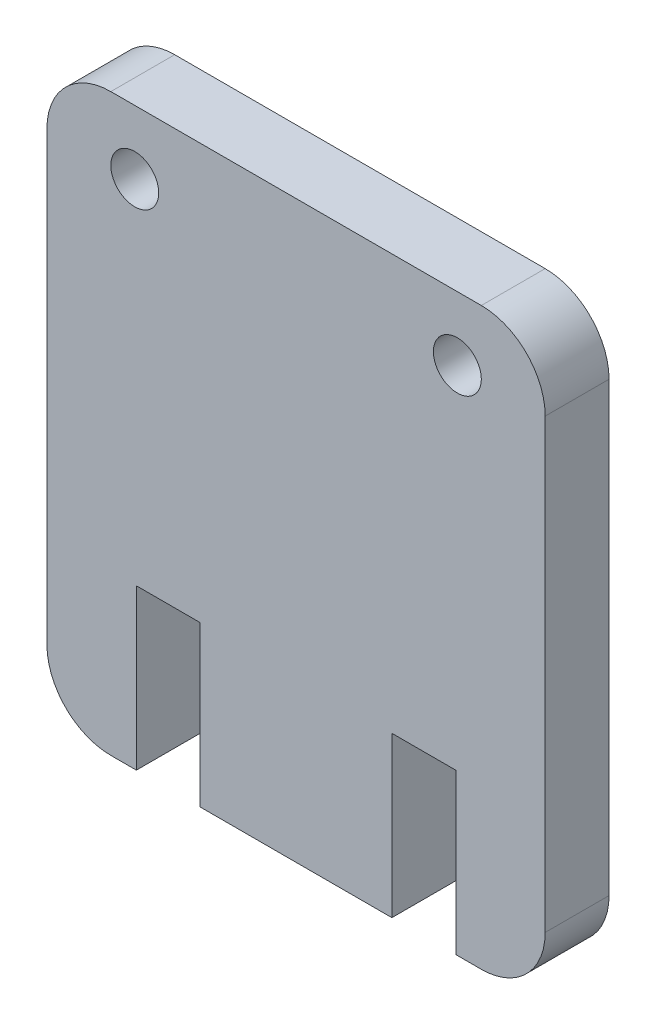
SolidWorks part; units mm, degrees
material "Acrylic (Medium-high impact)"
ref_plane "Front Plane" through (0, 0, 0) normal (0, 0, 1) x (1, 0, 0)
ref_plane "Top Plane" through (0, 0, 0) normal (0, 1, 0) x (1, 0, 0)
ref_plane "Right Plane" through (0, 0, 0) normal (1, 0, 0) x (0, 0, -1)
sketch "Model" plane through (0, 0, 0) normal (0, 0, 1) x (1, 0, 0)
  line L0 (2, 0) -> (2.8, 0)
  line L1 (2.8, 0) -> (2.8, 5)
  line L2 (2.8, 5) -> (4.8, 5)
  line L3 (4.8, 5) -> (4.8, 0)
  line L4 (4.8, 0) -> (10.8, 0)
  line L5 (10.8, 0) -> (10.8, 5)
  line L6 (10.8, 5) -> (12.8, 5)
  line L7 (12.8, 5) -> (12.8, 0)
  line L8 (12.8, 0) -> (13.6, 0)
  line L9 (0, 2) -> (0, 16)
  line L10 (2, 18) -> (13.6, 18)
  line L11 (15.6, 16) -> (15.6, 2)
  circle A0 centre (2.75, 16) radius 0.75
  circle A3 centre (12.85, 16) radius 0.75
  arc A4 (0, 16) -> (2, 18) centre (2, 16) cw
  arc A5 (2, 0) -> (0, 2) centre (2, 2) cw
  arc A6 (15.6, 2) -> (13.6, 0) centre (13.6, 2) cw
  arc A7 (13.6, 18) -> (15.6, 16) centre (13.6, 16) cw
  dimension "D1" = 1.5
  dimension "D2" = 2
  dimension "D3" = 15.6
  dimension "D4" = 13
  dimension "D5" = 6
  dimension "D6" = 2
  dimension "D10" = 5
other "AlignGroup1"
other "AlignGroup2"
other "AlignGroup3"
other "AlignGroup4"
other "AlignGroup5"
other "AlignGroup6"
other "AlignGroup7"
other "AlignGroup8"
extrude "Boss-Extrude1" add sketch "Model" along normal blind 2
